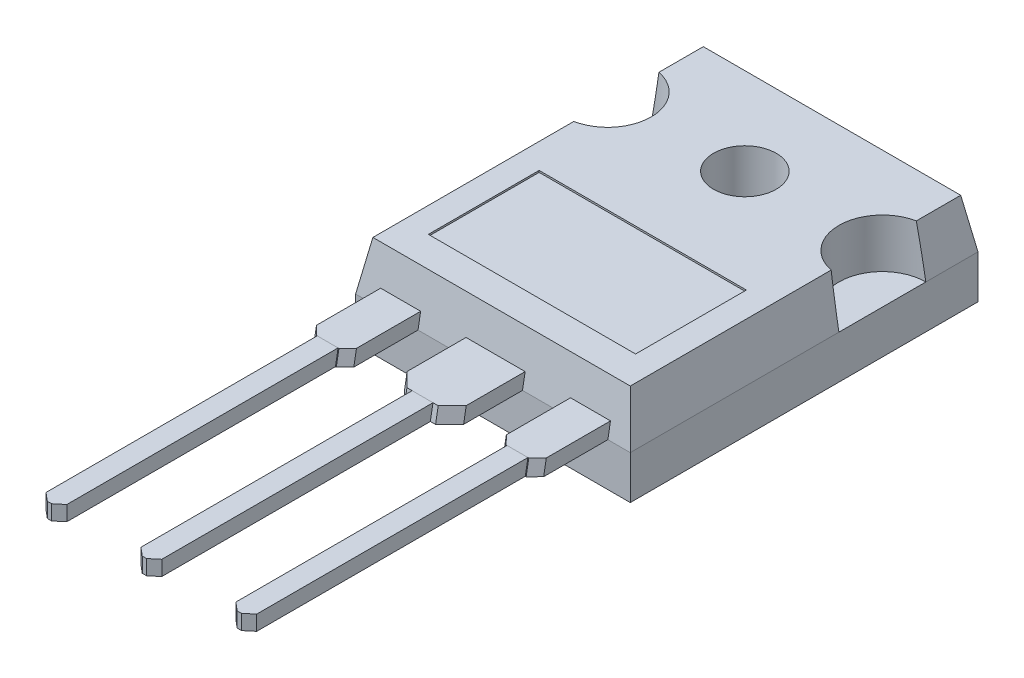
SolidWorks part; units mm, degrees
ref_plane "Front Plane" through (0, 0, 0) normal (0, 0, 1) x (1, 0, 0)
ref_plane "Top Plane" through (0, 0, 0) normal (0, 1, 0) x (1, 0, 0)
ref_plane "Right Plane" through (0, 0, 0) normal (1, 0, 0) x (0, 0, -1)
sketch "Sketch1" plane through (0, 0, 0) normal (0, 1, 0) x (1, 0, 0)
  line L1 (-7.9, 10) -> (7.9, 10)
  line L2 (-7.9, 10) -> (-7.9, -10)
  line L3 (-7.9, -10) -> (7.9, -10)
  line L4 (7.9, 10) -> (7.9, -10)
  line L5 (-7.9, 10) -> (7.9, -10) construction
  line L6 (-7.9, -10) -> (7.9, 10) construction
  point P0 (0, 0)
  dimension "D1" = 15.8
  dimension "D2" = 20
extrude "Boss-Extrude1" add sketch "Sketch1" along normal blind 2.49
sketch "Sketch2" plane through (0, 2.49, 0) normal (0, 1, 0) x (1, 0, 0)
  line L1 (-7.9, -10) -> (7.9, -10)
  line L2 (-7.9, -10) -> (-7.9, 10)
  line L3 (-7.9, 10) -> (7.9, 10)
  line L4 (7.9, -10) -> (7.9, 10)
  line L5 (-7.9, -10) -> (7.9, 10) construction
  line L6 (-7.9, 10) -> (7.9, -10) construction
  point P0 (0, 0)
extrude "Boss-Extrude3" add sketch "Sketch2" along normal blind 2.82 draft 10
sketch "Sketch4" plane through (0, 0, 0) normal (0, 0, 1) x (1, 0, 0)
  line L0 (0, 0) -> (0, 5.31) construction
  line L1 (-7.4028, 5.31) -> (7.4028, 5.31) construction
  line L2 (-7.9, 2.49) -> (7.9, 2.49) construction
  line L3 (-1.7, 3.35) -> (1.7, 3.35)
  line L4 (-1.7, 3.35) -> (-1.7, 2.49)
  line L5 (-1.7, 2.49) -> (1.7, 2.49)
  line L6 (1.7, 3.35) -> (1.7, 2.49)
  line L7 (-1.7, 3.35) -> (1.7, 2.49) construction
  line L8 (-1.7, 2.49) -> (1.7, 3.35) construction
  line L9 (-6.61, 3.35) -> (-6.61, 2.49)
  line L10 (4.31, 3.35) -> (6.61, 3.35)
  line L11 (4.31, 3.35) -> (4.31, 2.49)
  line L12 (4.31, 2.49) -> (6.61, 2.49)
  line L13 (6.61, 3.35) -> (6.61, 2.49)
  line L14 (4.31, 3.35) -> (6.61, 2.49) construction
  line L15 (4.31, 2.49) -> (6.61, 3.35) construction
  line L16 (-4.31, 2.49) -> (-6.61, 2.49)
  line L17 (-4.31, 3.35) -> (-4.31, 2.49)
  line L18 (-4.31, 3.35) -> (-6.61, 3.35)
  point P5 (0, 2.92)
  point P12 (5.46, 2.92)
  dimension "D1" = 3.4
  dimension "D2" = 0.86
  dimension "D3" = 5.46
  dimension "D4" = 2.3
extrude "Boss-Extrude4" add sketch "Sketch4" along normal blind 4.2 from surface starting at face at (0, 3.9, 9.7514)
sketch "Sketch5" plane through (0, 0, 0) normal (0, 0, 1) x (1, 0, 0)
  line L0 (1.7, 2.49) -> (-1.7, 2.49) construction
  line L1 (5.46, 0) -> (5.46, 5.31) construction
  line L2 (-0.6, 3.35) -> (0.6, 3.35)
  line L3 (-0.6, 3.35) -> (-0.6, 2.49)
  line L4 (-0.6, 2.49) -> (0.6, 2.49)
  line L5 (0.6, 3.35) -> (0.6, 2.49)
  line L6 (-0.6, 3.35) -> (0.6, 2.49) construction
  line L7 (-0.6, 2.49) -> (0.6, 3.35) construction
  line L8 (0, 0) -> (0, 5.31) construction
  line L9 (-7.4028, 5.31) -> (7.4028, 5.31) construction
  line L10 (6.61, 2.49) -> (4.31, 2.49) construction
  line L11 (4.86, 3.35) -> (6.06, 3.35)
  line L12 (4.86, 3.35) -> (4.86, 2.49)
  line L13 (4.86, 2.49) -> (6.06, 2.49)
  line L14 (6.06, 3.35) -> (6.06, 2.49)
  line L15 (4.86, 3.35) -> (6.06, 2.49) construction
  line L16 (4.86, 2.49) -> (6.06, 3.35) construction
  line L17 (-7.9, 0) -> (7.9, 0) construction
  line L18 (-4.86, 3.35) -> (-4.86, 2.49)
  line L19 (-4.86, 3.35) -> (-6.06, 3.35)
  line L20 (-6.06, 3.35) -> (-6.06, 2.49)
  line L21 (-4.86, 2.49) -> (-6.06, 2.49)
  point P0 (0, 2.92)
  point P12 (5.46, 2.92)
  dimension "D1" = 1.2
  dimension "D2" = 1.2
extrude "Boss-Extrude6" add sketch "Sketch5" along normal blind 16 from vertex separate body starting at point (6.61, 3.35, 14.0484)
sketch "Sketch6" plane through (0, 5.31, 0) normal (0, 1, 0) x (1, 0, 0)
  circle A0 centre (0, 4.49) radius 1.8
  dimension "D2" = 3.6
  dimension "D1" = 5.51
extrude "Cut-Extrude1" cut sketch "Sketch6" against normal through all
sketch "Sketch7" plane through (0, 5.31, 0) normal (0, 1, 0) x (1, 0, 0)
  line L0 (0, 0) -> (0, 10) construction
  line L1 (7.9, 10) -> (-7.9, 10) construction
  line L3 (7.9, -10) -> (7.9, 10) construction
  circle A0 centre (7.9, 4.5) radius 2.5
  circle A1 centre (-7.9, 4.5) radius 2.5
  dimension "D2" = 5
  dimension "D1" = 5.5
extrude "Cut-Extrude2" cut sketch "Sketch7" against normal up to vertex (2.82 mm away) up to point (7.9, 2.49, 10)
chamfer "Chamfer2" distance 0.5 angle 45 4 edges at (6.61, 2.92, 14.1242) (4.31, 2.92, 14.1242) (-4.31, 2.92, 14.1242) (-6.61, 2.92, 14.1242)
chamfer "Chamfer3" distance 0.8 angle 45 2 edges at (1.7, 2.92, 14.1242) (-1.7, 2.92, 14.1242)
chamfer "Chamfer7" distance 0.4 angle 50 2 edges at (0.6, 2.92, 30.0484) (-0.6, 2.92, 30.0484) first distance on face at (0.6, 2.92, 22.0484) first distance on face at (-0.6, 2.92, 22.0484)
chamfer "Chamfer8" distance 0.4 angle 50 2 edges at (-4.86, 2.92, 30.0484) (-6.06, 2.92, 30.0484) first distance on face at (-4.86, 2.92, 22.0484) first distance on face at (-6.06, 2.92, 22.0484)
chamfer "Chamfer9" distance 0.4 angle 50 2 edges at (6.06, 2.92, 30.0484) (4.86, 2.92, 30.0484) first distance on face at (6.06, 2.92, 22.0484) first distance on face at (4.86, 2.92, 22.0484)
sketch "Sketch9" plane through (0, 0, 0) normal (0, -1, 0) x (1, 0, 0)
  line L1 (-6.4932, 7.0481) -> (6.4932, 7.0481)
  line L2 (-6.4932, 7.0481) -> (-6.4932, -8.3924)
  line L3 (-6.4932, -8.3924) -> (6.4932, -8.3924)
  line L4 (6.4932, 7.0481) -> (6.4932, -8.3924)
  line L5 (-6.4932, 7.0481) -> (6.4932, -8.3924) construction
  line L6 (-6.4932, -8.3924) -> (6.4932, 7.0481) construction
  point P0 (0, -0.6721)
extrude "Cut-Extrude3" cut sketch "Sketch9" against normal up to vertex (2.49 mm away) up to point (7.9, 2.49, -2)
sketch "Sketch10" plane through (0, 2.49, 0) normal (0, -1, 0) x (1, 0, 0)
  line L1 (-6.4932, 7.0481) -> (6.4932, 7.0481)
  line L2 (-6.4932, 7.0481) -> (-6.4932, -8.3924)
  line L3 (-6.4932, -8.3924) -> (6.4932, -8.3924)
  line L4 (6.4932, 7.0481) -> (6.4932, -8.3924)
extrude "Boss-Extrude7" add sketch "Sketch10" along normal up to surface (2.49 mm away) up to face at (0, 0, -0.6721)
sketch "Sketch13" plane through (0, 2.49, 0) normal (0, 1, 0) x (1, 0, 0)
  circle A0 centre (0, 4.49) radius 1.8
extrude "Cut-Extrude4" cut sketch "Sketch13" against normal up to surface (2.49 mm away) up to face at (0, 0, 0)
sketch "Sketch14" plane through (0, 5.31, 0) normal (0, 1, 0) x (1, 0, 0)
  line L1 (-5.9596, -1.3833) -> (5.9596, -1.3833)
  line L2 (-5.9596, -1.3833) -> (-5.9596, -7.7559)
  line L3 (-5.9596, -7.7559) -> (5.9596, -7.7559)
  line L4 (5.9596, -1.3833) -> (5.9596, -7.7559)
  line L5 (-5.9596, -1.3833) -> (5.9596, -7.7559) construction
  line L6 (-5.9596, -7.7559) -> (5.9596, -1.3833) construction
  point P0 (0, -4.5696)
extrude "Cut-Extrude5" cut sketch "Sketch14" against normal blind 0.1
